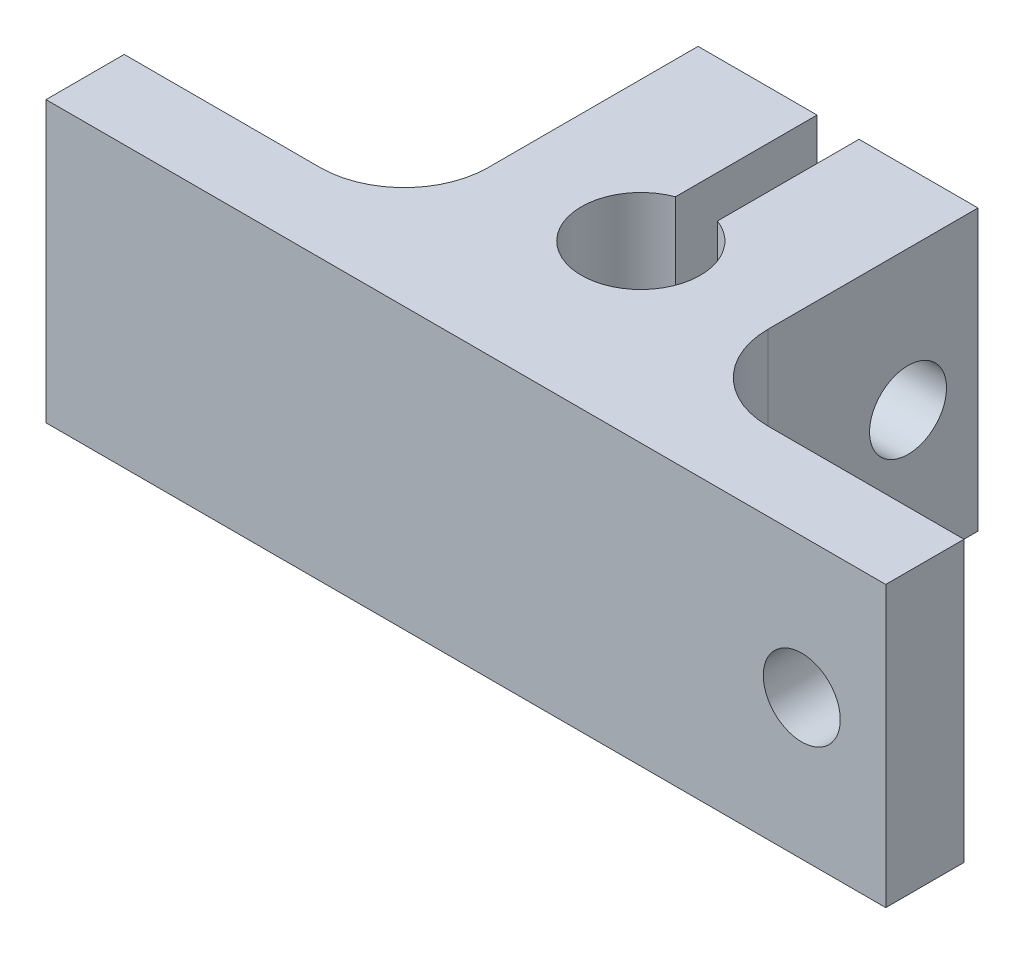
SolidWorks part; units mm, degrees
ref_plane "Front Plane" through (0, 0, 0) normal (0, 0, 1) x (1, 0, 0)
ref_plane "Top Plane" through (0, 0, 0) normal (0, 1, 0) x (1, 0, 0)
ref_plane "Right Plane" through (0, 0, 0) normal (1, 0, 0) x (0, 0, -1)
sketch "Sketch1" plane through (0, 0, 0) normal (0, 1, 0) x (1, 0, 0)
  line L0 (30, -12.5) -> (-30, -12.5)
  line L5 (-30, -12.5) -> (-30, -6.9096)
  line L7 (0, -47.9589) -> (0, -6.9096) construction
  line L8 (30, -12.5) -> (30, -6.9096)
  line L10 (-30, -6.9096) -> (-16, -6.9096)
  line L13 (16, -6.9096) -> (30, -6.9096)
  line L14 (0, -4.25) -> (0, 12.5) construction
  line L15 (-10, -0.9096) -> (-10, 14.0904)
  line L16 (-1.5, 14.0904) -> (-1.5, 3.9765)
  line L17 (-10, 14.0904) -> (-1.5, 14.0904)
  line L18 (1.5, 14.0904) -> (1.5, 3.9765)
  line L19 (10, -0.9096) -> (10, 14.0904)
  line L20 (10, 14.0904) -> (1.5, 14.0904)
  arc A0 (-1.5, 3.9765) -> (1.5, 3.9765) centre (0, 0) ccw
  arc A3 (10, -0.9096) -> (16, -6.9096) centre (16, -0.9096) ccw
  arc A4 (-10, -0.9096) -> (-16, -6.9096) centre (-16, -0.9096) cw
  point P17 (10, -6.9096)
  dimension "D1" = 8.5
  dimension "D2" = 12.5
  dimension "D4" = 15
  dimension "D5" = 6
  dimension "D3" = 60
  dimension "1.5" = 1.5
extrude "Boss-Extrude1" add sketch "Sketch1" along normal blind 20
sketch "Sketch2" plane through (0, 0, 6.9096) normal (0, 0, -1) x (-1, 0, 0)
  line L0 (-30, 10) -> (30, 10) construction
  line L1 (-30, 20) -> (-30, 0) construction
  line L2 (30, 20) -> (30, 0) construction
  line L3 (5.75, 0) -> (5.75, 20) construction
  line L4 (1.5, 0) -> (10, 0) construction
  line L5 (1.5, 20) -> (10, 20) construction
  circle A0 centre (-24, 10) radius 2.75
  circle A1 centre (35.5, 10) radius 2.75
  dimension "D1" = 5.5
  dimension "D2" = 6
extrude "Cut-Extrude1" cut sketch "Sketch2" against normal through all
sketch "Sketch3" plane through (10, 0, 0) normal (1, 0, 0) x (0, 0, -1)
  line L0 (14.0904, 10) -> (-0.9096, 10) construction
  line L1 (14.0904, 20) -> (14.0904, 0) construction
  line L2 (-0.9096, 20) -> (-0.9096, 0) construction
  circle A0 centre (9.0904, 10) radius 2.75
  point P8 (0, 0)
  point P9 (0, 0)
  point P12 (0, 0)
  point P15 (0, 0)
  point P16 (0, 0)
  dimension "D1" = 5.5
  dimension "D2" = 5
extrude "Cut-Extrude2" cut sketch "Sketch3" against normal through all
